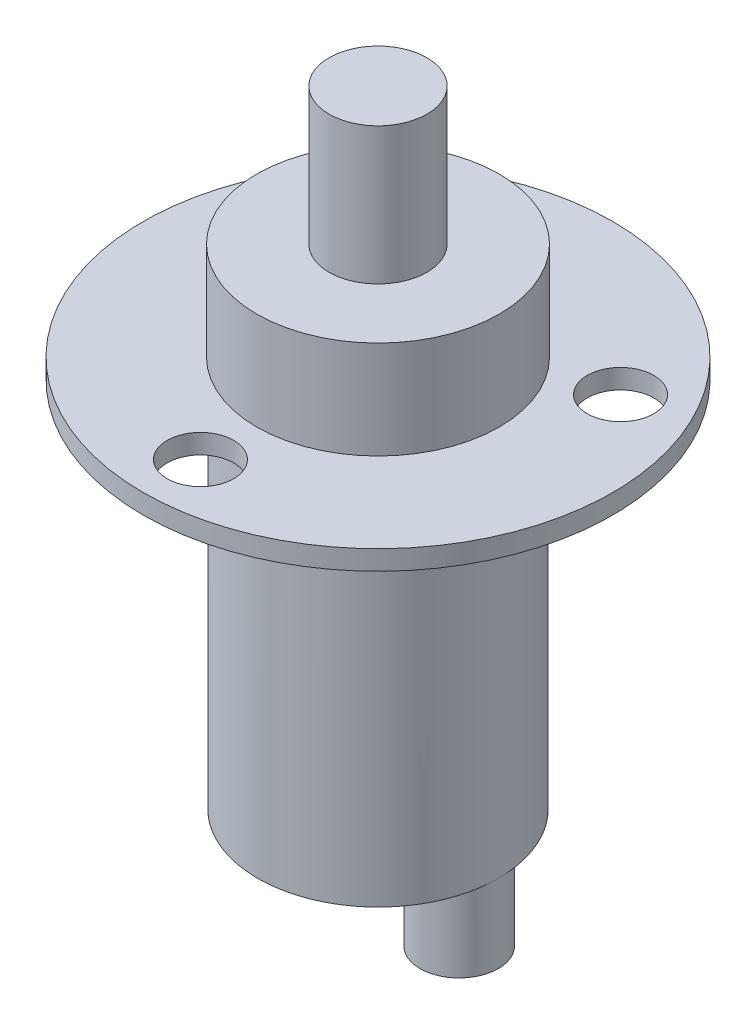
SolidWorks part; units mm, degrees
ref_plane "Front Plane" through (0, 0, 0) normal (0, 0, 1) x (1, 0, 0)
ref_plane "Top Plane" through (0, 0, 0) normal (0, 1, 0) x (1, 0, 0)
ref_plane "Right Plane" through (0, 0, 0) normal (1, 0, 0) x (0, 0, -1)
sketch "Sketch1" plane through (0, 0, 0) normal (0, 1, 0) x (1, 0, 0)
  circle A0 centre (0, 0) radius 6.15
  dimension "D1" = 12.3
extrude "Boss-Extrude1" add sketch "Sketch1" along normal blind 19
sketch "Sketch2" plane through (0, 19, 0) normal (0, 1, 0) x (1, 0, 0)
  circle A0 centre (0, 0) radius 12
  dimension "D1" = 24
extrude "Boss-Extrude2" add sketch "Sketch2" along normal blind 1
sketch "Sketch3" plane through (0, 20, 0) normal (0, 1, 0) x (1, 0, 0)
  circle A0 centre (0, 0) radius 6.2
  dimension "D1" = 12.4
extrude "Boss-Extrude3" add sketch "Sketch3" along normal blind 5
sketch "Sketch4" plane through (0, 25, 0) normal (0, 1, 0) x (1, 0, 0)
  circle A0 centre (0, 0) radius 2.5
  dimension "D1" = 5
extrude "Boss-Extrude4" add sketch "Sketch4" along normal blind 7
sketch "Sketch5" plane through (0, 0, 0) normal (0, -1, 0) x (1, 0, 0)
  circle A0 centre (-4.15, 0) radius 2
  circle A1 centre (4.15, 0) radius 2
  circle A2 centre (0, 0) radius 6.15 construction
  circle A3 centre (0, 0) radius 6.15 construction
  dimension "D1" = 4
extrude "Boss-Extrude5" add sketch "Sketch5" along normal blind 4
sketch "Sketch6" plane through (0, 19, 0) normal (0, -1, 0) x (1, 0, 0)
  circle A0 centre (0, 9.075) radius 1.5
  circle A1 centre (0, 0) radius 12 construction
  arc A2 (6.15, 0) -> (-6.15, 0) centre (0, 0) ccw construction
  circle A3 centre (0, 0) radius 12
  arc A4 (6.15, 0) -> (-6.15, 0) centre (0, 0) ccw
  circle A5 centre (0, 0) radius 9.075 construction
  circle A6 centre (7.8592, -4.5375) radius 1.5
  circle A7 centre (-7.8592, -4.5375) radius 1.5
  point P16 (0, 0)
  dimension "D1" = 3
  dimension "D2" = 24
  dimension "D3" = 6.15
  dimension "D4" = 18.15
  dimension "D5" = 3
extrude "Cut-Extrude1" cut sketch "Sketch6" against normal through all contours A0 | A6 | A7 region at (0, 19, 9.075) region at (7.8592, 19, -4.5375) region at (-7.8592, 19, -4.5375)
hole_wizard "M3 Clearance Hole1" positions "Sketch7" profile "Sketch9" hole size "M3" standard "DIN" end condition through all
sketch "Sketch7" plane through (0, 20, 0) normal (0, 1, 0) x (1, 0, 0)
  point P0 (7.8592, 4.5375)
  point P3 (-7.8592, 4.5375)
  point P6 (0, -9.075)
sketch "Sketch9" plane through (7.8592, 20, -4.5375) normal (1, 0, 0) x (0, 0, 1)
  line L0 (0, 0) -> (0, 24)
  line L1 (0, 24) -> (1.7, 24)
  line L2 (1.7, 24) -> (1.7, 0)
  line L5 (1.7, 0) -> (0, 0)
  line L11 (0, -6.35) -> (0, 107.95) construction
  dimension "Thru Hole Dia." = 3.4
  dimension "Thru Hole Depth" = 24
equation "\"D4@Sketch6\"=(\"D2@Sketch6\"+2*\"D3@Sketch6\")/2"
